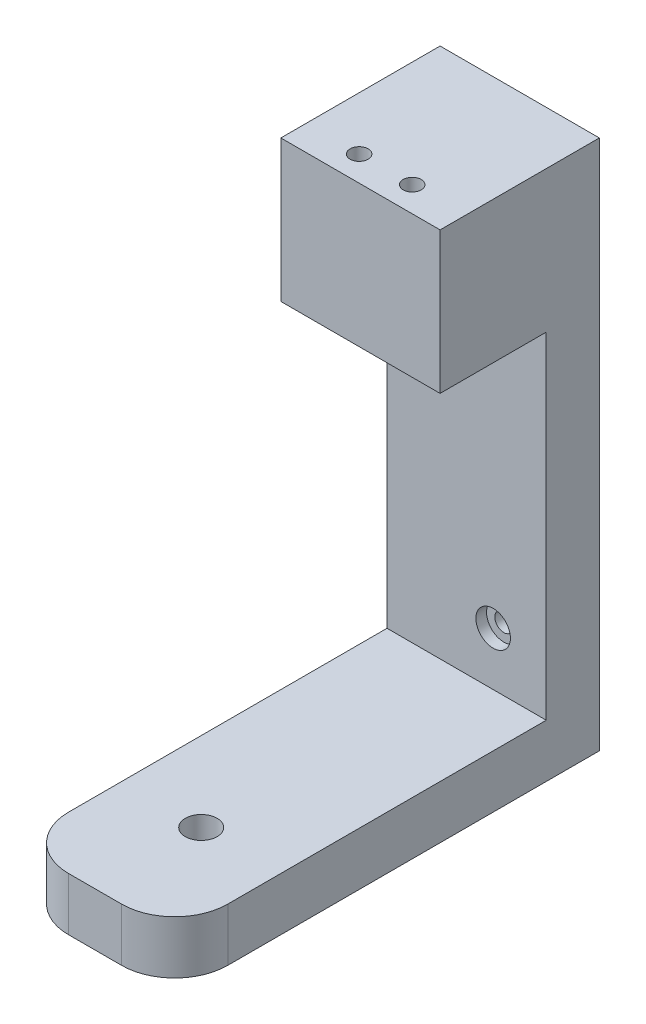
SolidWorks part; units mm, degrees
ref_plane "Plan de face" through (0, 0, 0) normal (0, 0, 1) x (1, 0, 0)
ref_plane "Plan de dessus" through (0, 0, 0) normal (0, 1, 0) x (1, 0, 0)
ref_plane "Plan de droite" through (0, 0, 0) normal (1, 0, 0) x (0, 0, -1)
sketch "Esquisse1" plane through (0, 0, 0) normal (0, 0, 1) x (1, 0, 0)
  line L1 (0, 0) -> (30, 0)
  line L2 (0, 0) -> (0, 100)
  line L3 (0, 100) -> (30, 100)
  line L4 (30, 0) -> (30, 100)
  dimension "D1" = 30
  dimension "D2" = 100
extrude "Boss.-Extru.1" add sketch "Esquisse1" along normal blind 10
sketch "Esquisse2" plane through (0, 0, 10) normal (0, 0, 1) x (1, 0, 0)
  line L0 (30, 0) -> (30, 100) construction
  line L1 (0, 0) -> (30, 0) construction
  line L2 (0, 100) -> (0, 0) construction
  line L3 (30, 0) -> (30, 10)
  line L4 (0, 0) -> (30, 0)
  line L5 (0, 10) -> (0, 0)
  line L6 (0, 10) -> (30, 10)
  dimension "D1" = 10
extrude "Boss.-Extru.2" add sketch "Esquisse2" along normal blind 70
sketch "Esquisse3" plane through (0, 0, 0) normal (0, -1, 0) x (1, 0, 0)
  line L0 (0, 80) -> (0, 0) construction
  line L1 (0, 0) -> (30, 0) construction
  circle A0 centre (15, 60) radius 3
  dimension "D3" = 6
  dimension "D1" = 15
  dimension "D2" = 60
extrude "Enlèv. mat.-Extru.1" cut sketch "Esquisse3" against normal up to surface (10 mm away) up to face at (15, 10, 45)
sketch "Esquisse4" plane through (0, 0, 10) normal (0, 0, 1) x (1, 0, 0)
  line L0 (30, 10) -> (30, 100) construction
  line L1 (30, 73.32) -> (30, 100)
  line L2 (0, 100) -> (0, 10) construction
  line L3 (30, 100) -> (0, 100) construction
  line L4 (0, 100) -> (0, 73.32)
  line L5 (30, 100) -> (0, 100)
  line L6 (0, 73.32) -> (30, 73.32)
  dimension "D1" = 26.68
extrude "Boss.-Extru.3" add sketch "Esquisse4" along normal blind 20
sketch "Esquisse5" plane through (0, 73.32, 0) normal (0, -1, 0) x (1, 0, 0)
  line L0 (0, 30) -> (0, 10) construction
  line L2 (0, 30) -> (30, 30) construction
  circle A0 centre (10, 25.25) radius 2.2
  circle A1 centre (20, 25.25) radius 2.2
  dimension "D3" = 4.4
  dimension "D4" = 4.4
  dimension "D1" = 10
  dimension "D2" = 10
  dimension "D5" = 4.75
  dimension "D6" = 4.75
hole_wizard "Dégagement M31" positions "Esquisse8" profile "Esquisse7" hole size "M3" standard "ISO"
sketch "Esquisse8" plane through (0, 73.32, 0) normal (0, -1, 0) x (-1, 0, 0)
  point P0 (-10, -25.25)
  point P3 (-20, -25.25)
sketch "Esquisse7" plane through (10, 73.32, 25.25) normal (1, 0, 0) x (0, 0, -1)
  line L0 (0, 0) -> (0, 27.7015)
  line L1 (0, 27.7015) -> (1.7, 26.68)
  line L2 (1.7, 26.68) -> (1.7, 0)
  line L5 (1.7, 0) -> (0, 0)
  line L10 (0, 27.7015) -> (-1.7, 26.68) construction
  line L11 (0, -6.35) -> (0, 107.95) construction
  dimension "Diamètre du perçage" = 3.4
  dimension "Profondeur du perçage" = 26.68
  dimension "Angle de pointe" = 118
sketch "Esquisse9" plane through (0, 0, 10) normal (0, 0, 1) x (1, 0, 0)
  line L0 (0, 73.32) -> (0, 10) construction
  line L1 (30, 10) -> (30, 73.32) construction
  line L2 (30, 10) -> (0, 10) construction
  line L3 (0, 73.32) -> (30, 73.32) construction
  circle A1 centre (20, 20) radius 1.5
  circle A2 centre (10, 63.32) radius 1.5
  dimension "D2" = 3
  dimension "D4" = 3
  dimension "D1" = 10
  dimension "D3" = 10
  dimension "D5" = 10
  dimension "D6" = 10
hole_wizard "Chambrage pour tête cylindrique fendue M31" positions "Esquisse10" profile "Esquisse12" counterbore size "M3" standard "ISO"
sketch "Esquisse10" plane through (0, 0, 10) normal (0, 0, 1) x (1, 0, 0)
  point P0 (10, 63.32)
  point P3 (20, 20)
sketch "Esquisse12" plane through (10, 63.32, 10) normal (1, 0, 0) x (0, -1, 0)
  line L0 (0, 0) -> (0, 11.0215)
  line L1 (0, 11.0215) -> (1.7, 10)
  line L2 (1.7, 10) -> (1.7, 2)
  line L3 (1.7, 2) -> (3.25, 2)
  line L4 (3.25, 2) -> (3.25, 0)
  line L5 (3.25, 0) -> (0, 0)
  line L10 (0, 11.0215) -> (-1.7, 10) construction
  line L11 (0, -6.35) -> (0, 107.95) construction
  dimension "Diamètre du perçage" = 3.4
  dimension "Profondeur du perçage" = 10
  dimension "Diamètre du chambrage" = 6.5
  dimension "Profondeur du chambrage" = 2
  dimension "Angle de pointe" = 118
fillet "Congé1" radius 10 2 edges at (30, 5, 80) (0, 5, 80)
equation "\"D4@Esquisse5\"=\"D3@Esquisse5\""
equation "\"D6@Esquisse5\"=\"D5@Esquisse5\""
